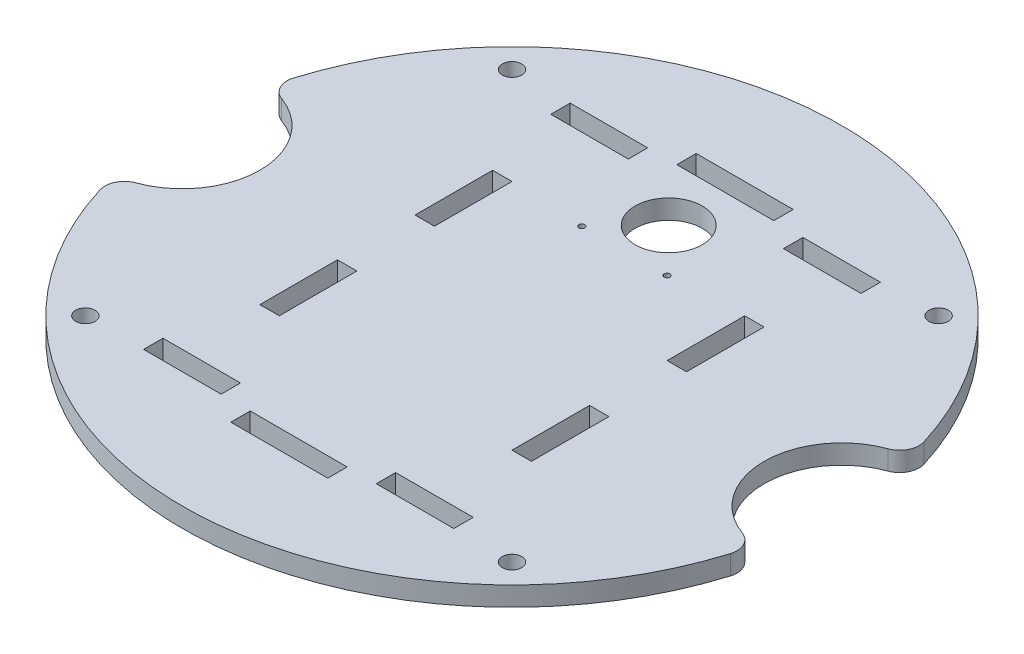
SolidWorks part; units mm, degrees
material "Pine"
ref_plane "Front Plane" through (0, 0, 0) normal (0, 0, 1) x (1, 0, 0)
ref_plane "Top Plane" through (0, 0, 0) normal (0, 1, 0) x (1, 0, 0)
ref_plane "Right Plane" through (0, 0, 0) normal (1, 0, 0) x (0, 0, -1)
sketch "Sketch1" plane through (0, 0, 0) normal (0, 1, 0) x (1, 0, 0)
  line L0 (0, 0) -> (0, 123.9148) construction
  line L1 (0, 0) -> (144.4711, 0) construction
  line L2 (-50.8, 63.5) -> (-25.4, 63.5)
  line L3 (-50.8, 63.5) -> (-50.8, 69.85)
  line L4 (-50.8, 69.85) -> (-25.4, 69.85)
  line L5 (-25.4, 63.5) -> (-25.4, 69.85)
  line L6 (25.4, 63.5) -> (25.4, 69.85)
  line L7 (50.8, 69.85) -> (25.4, 69.85)
  line L8 (50.8, 63.5) -> (50.8, 69.85)
  line L9 (50.8, 63.5) -> (25.4, 63.5)
  line L10 (-25.4, -63.5) -> (-25.4, -69.85)
  line L11 (-50.8, -63.5) -> (-25.4, -63.5)
  line L12 (-50.8, -63.5) -> (-50.8, -69.85)
  line L13 (-50.8, -69.85) -> (-25.4, -69.85)
  line L14 (50.8, -63.5) -> (50.8, -69.85)
  line L15 (50.8, -69.85) -> (25.4, -69.85)
  line L16 (25.4, -63.5) -> (25.4, -69.85)
  line L17 (50.8, -63.5) -> (25.4, -63.5)
  line L18 (38.1, -38.1) -> (44.45, -38.1)
  line L19 (38.1, 38.1) -> (44.45, 38.1)
  line L20 (38.1, 38.1) -> (38.1, 12.7)
  line L21 (38.1, 12.7) -> (44.45, 12.7)
  line L22 (44.45, 38.1) -> (44.45, 12.7)
  line L23 (38.1, -38.1) -> (38.1, -12.7)
  line L24 (38.1, -12.7) -> (44.45, -12.7)
  line L25 (44.45, -38.1) -> (44.45, -12.7)
  line L26 (-38.1, -38.1) -> (-44.45, -38.1)
  line L27 (-44.45, -38.1) -> (-44.45, -12.7)
  line L28 (-38.1, -38.1) -> (-38.1, -12.7)
  line L29 (-38.1, -12.7) -> (-44.45, -12.7)
  line L30 (-38.1, 12.7) -> (-44.45, 12.7)
  line L31 (-38.1, 38.1) -> (-38.1, 12.7)
  line L32 (-38.1, 38.1) -> (-44.45, 38.1)
  line L33 (-44.45, 38.1) -> (-44.45, 12.7)
  line L34 (-15.875, 69.85) -> (-15.875, 76.2)
  line L35 (15.875, -69.85) -> (-15.875, -69.85)
  line L36 (15.875, -69.85) -> (15.875, -76.2)
  line L37 (15.875, -76.2) -> (-15.875, -76.2)
  line L38 (-15.875, -69.85) -> (-15.875, -76.2)
  line L39 (15.875, -69.85) -> (-15.875, -76.2) construction
  line L40 (15.875, -76.2) -> (-15.875, -69.85) construction
  line L41 (15.875, 76.2) -> (-15.875, 76.2)
  line L42 (15.875, 69.85) -> (15.875, 76.2)
  line L43 (15.875, 69.85) -> (-15.875, 69.85)
  arc A0 (-103.1875, -31.7103) -> (103.1875, -31.7103) centre (0, 0) ccw
  circle A1 centre (0, 51.308) radius 10.9982
  arc A2 (-99.2841, -23.876) -> (-99.2841, 23.876) centre (-107.95, 0) ccw
  arc A3 (-99.2841, 23.876) -> (-103.1875, 31.7103) centre (-97.1176, 29.845) cw
  arc A4 (-99.2841, -23.876) -> (-103.1875, -31.7103) centre (-97.1176, -29.845) ccw
  arc A5 (99.2841, -23.876) -> (103.1875, -31.7103) centre (97.1176, -29.845) cw
  arc A6 (99.2841, -23.876) -> (99.2841, 23.876) centre (107.95, 0) cw
  arc A7 (99.2841, 23.876) -> (103.1875, 31.7103) centre (97.1176, 29.845) ccw
  arc A8 (103.1875, 31.7103) -> (-103.1875, 31.7103) centre (0, 0) ccw
  arc A9 (-24.781, 52.3984) -> (-24.6224, 50.8693) centre (3.7105, 54.5813) ccw construction
  arc A11 (4.4568, 49.2663) -> (5.9747, 49.1574) centre (5.3701, 51.3619) ccw construction
  circle A12 centre (13.97, 36.83) radius 0.9525
  circle A13 centre (-13.97, 36.83) radius 0.9525
  circle A14 centre (13.97, 36.83) radius 0.9525 construction
  point P52 (0, -73.025)
  point P61 (-24.712, 51.6327)
  point P66 (5.2064, 49.0818)
  dimension "D1" = 215.9
  dimension "D10" = 21.9964
  dimension "D12" = 50.8
  dimension "D13" = 6.35
  dimension "D14" = 6.35
  dimension "D11" = 51.308
  dimension "D2" = 25.4
  dimension "D3" = 25.4
  dimension "D4" = 6.35
  dimension "D5" = 63.5
  dimension "D6" = 6.35
  dimension "D7" = 25.4
  dimension "D8" = 12.7
  dimension "D9" = 38.1
  dimension "D15" = 31.75
  dimension "D16" = 6.35
extrude "Boss-Extrude1" add sketch "Sketch1" along normal blind 6.35
sketch "Sketch2" plane through (0, 0, 0) normal (0, -1, 0) x (1, 0, 0)
  line L0 (0, 0) -> (0, 99.3828) construction
  line L1 (0, 0) -> (-150.0844, 0) construction
  circle A0 centre (-69.85, 69.85) radius 3.175
  circle A1 centre (69.85, 69.85) radius 3.175
  circle A2 centre (69.85, -69.85) radius 3.175
  circle A3 centre (-69.85, -69.85) radius 3.175
  dimension "D1" = 6.35
extrude "Cut-Extrude1" cut sketch "Sketch2" against normal up to surface (6.35 mm away) up to face at (0, 6.35, 73.025)
